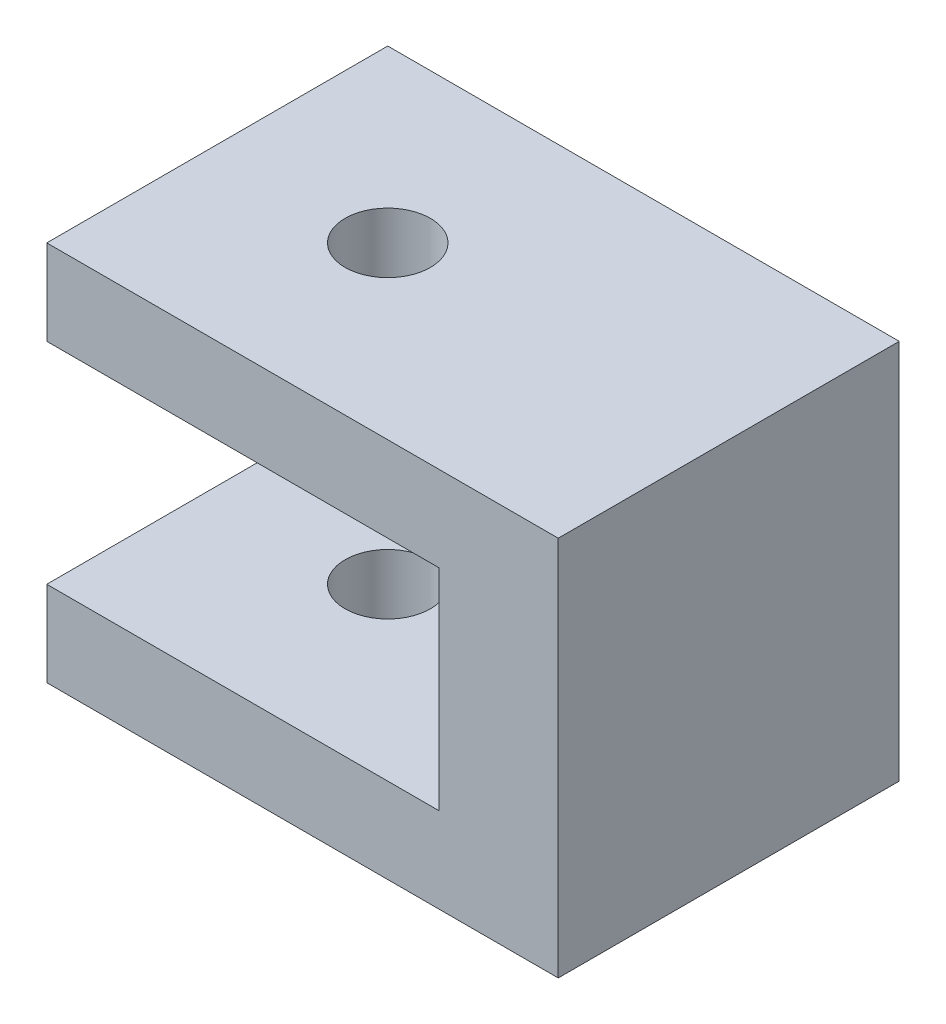
SolidWorks part; units mm, degrees
ref_plane "Front Plane" through (0, 0, 0) normal (0, 0, 1) x (1, 0, 0)
ref_plane "Top Plane" through (0, 0, 0) normal (0, 1, 0) x (1, 0, 0)
ref_plane "Right Plane" through (0, 0, 0) normal (1, 0, 0) x (0, 0, -1)
sketch "Sketch1" plane through (0, 0, 0) normal (0, 1, 0) x (1, 0, 0)
  line L1 (-15, -10) -> (15, -10)
  line L2 (-15, -10) -> (-15, 10)
  line L3 (-15, 10) -> (15, 10)
  line L4 (15, -10) -> (15, 10)
  line L5 (-15, -10) -> (15, 10) construction
  line L6 (-15, 10) -> (15, -10) construction
  point P0 (0, 0)
  point P6 (0, 0)
  point P8 (0, 0)
  point P9 (0, 0)
  point P10 (0, 0)
  point P11 (0, 0)
  point P12 (8.2491, -10)
  point P13 (8.2116, -10)
  dimension "D1" = 30
  dimension "D2" = 20
extrude "Boss-Extrude1" add sketch "Sketch1" along normal blind 5
sketch "Sketch2" plane through (0, 5, 0) normal (0, 1, 0) x (1, 0, 0)
  line L0 (15, -10) -> (15, 10)
  line L1 (15, 10) -> (8, 10)
  line L2 (15, 10) -> (-15, 10) construction
  line L3 (8, 10) -> (8, -10)
  line L4 (-15, -10) -> (15, -10) construction
  line L5 (8, -10) -> (15, -10)
  dimension "D1" = 7
extrude "Boss-Extrude2" add sketch "Sketch2" along normal blind 17.34
sketch "Sketch3" plane through (8, 0, 0) normal (-1, 0, 0) x (0, 0, 1)
  line L0 (-10, 22.34) -> (10, 22.34)
  line L1 (10, 22.34) -> (10, 17.34)
  line L2 (10, 22.34) -> (10, 5) construction
  line L3 (10, 17.34) -> (-10, 17.34)
  line L4 (-10, 22.34) -> (-10, 5) construction
  line L5 (-10, 17.34) -> (-10, 22.34)
  dimension "D1" = 5
extrude "Boss-Extrude3" add sketch "Sketch3" along normal up to surface (23 mm away) up to face at (-15, 2.5, 0)
sketch "Sketch4" plane through (0, 22.34, 0) normal (0, 1, 0) x (1, 0, 0)
  line L0 (-15, 10) -> (-15, -10) construction
  line L3 (-15, -10) -> (15, -10) construction
  circle A0 centre (-5, 0) radius 2.5
  point P4 (0, 0)
  dimension "D1" = 10
  dimension "D3" = 5
  dimension "D2" = 10
extrude "Cut-Extrude1" cut sketch "Sketch4" against normal through all and the other way through all
